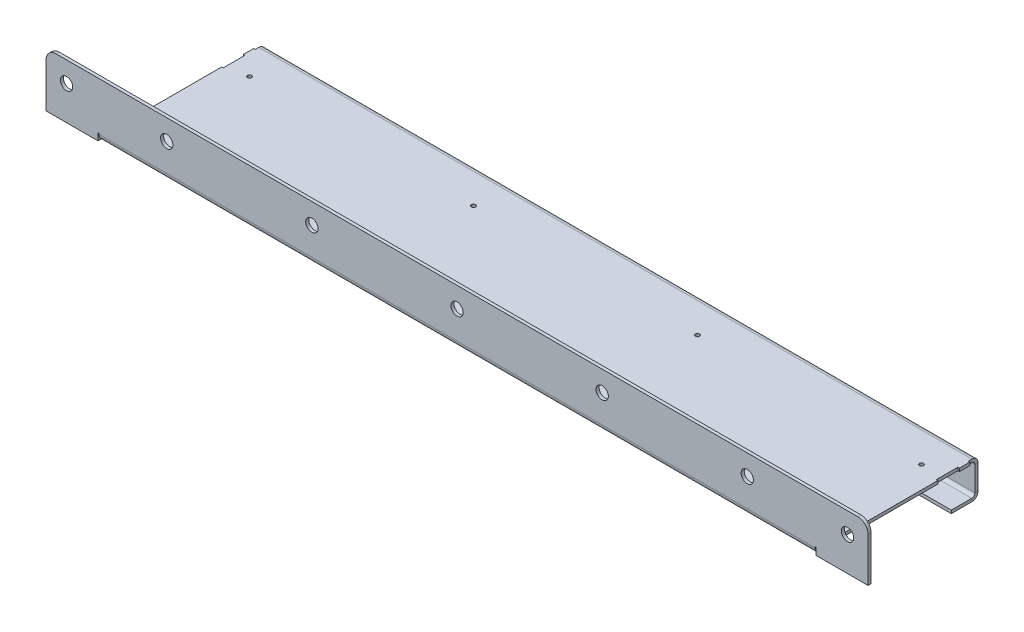
SolidWorks part; units mm, degrees
note: The reader was unsure of these and kept them because the rebuilt part matched: thickness of "Base-Flange1", "Edge-Flange1", "Edge-Flange2", "Edge-Flange3", "Sheet-Metal5", "Sheet-Metal6", "Sheet-Metal7", "Sheet-Metal8", "Sheet-Metal11", "Sheet-Metal12", "Sheet-Metal13", "Sheet-Metal15", "Sheet-Metal16", "Sheet-Metal17", "Sheet-Metal18"; flange length of "Edge-Flange1", "Edge-Flange2", "Edge-Flange3".
material "3.0 mm SS316 2B/2B"
ref_plane "Front Plane" through (0, 0, 0) normal (0, 0, 1) x (1, 0, 0)
ref_plane "Top Plane" through (0, 0, 0) normal (0, 1, 0) x (1, 0, 0)
ref_plane "Right Plane" through (0, 0, 0) normal (1, 0, 0) x (0, 0, -1)
sketch "Sketch2" plane through (0, 0, 0) normal (0, 0, 1) x (1, 0, 0)
  line L0 (400, 26.5) -> (-400, -26.5) construction
  line L1 (400, 26.5) -> (-400, 26.5)
  line L2 (400, 26.5) -> (400, -26.5)
  line L3 (400, -26.5) -> (-400, -26.5)
  line L4 (-400, 26.5) -> (-400, -26.5)
  line L5 (-400, 26.5) -> (400, -26.5) construction
  dimension "D1" = 800
  dimension "D2" = 53
base flange "Base-Flange1" sketch "Sketch2" thickness 3 reverse thickness direction no parameters "D1"=3
edge flange "Edge-Flange1" sketch "Sketch9" flange angle 90 flange length 160 flange position material inside bend radius 3 thickness 3 relief rectangular parameters "D1"=2, "D6"=10
sketch "Sketch9" plane through (0, -26.5, -3) normal (0, 1, 0) x (1, 0, 0)
  line L0 (-348.5, 16.5) -> (-347, 16.5)
  line L1 (400, 0) -> (-400, 0) construction
  line L2 (-348.5, 0) -> (-348.5, 16.5)
  line L3 (-347, 157) -> (347, 157)
  line L4 (-400, -3) -> (400, -3) construction
  line L5 (348.5, 0) -> (-348.5, 0)
  line L6 (0, 0) -> (0, 157) construction
  line L7 (-347, 16.5) -> (-347, 37.5)
  line L8 (-347, 37.5) -> (-348.5, 37.5)
  line L9 (-348.5, 116.5) -> (-347, 116.5)
  line L10 (-347, 116.5) -> (-347, 137.5)
  line L11 (-347, 137.5) -> (-348.5, 137.5)
  line L12 (-348.5, 147.5) -> (-347, 147.5)
  line L13 (-347, 147.5) -> (-347, 157)
  line L14 (-348.5, 137.5) -> (-348.5, 147.5)
  line L15 (-348.5, 37.5) -> (-348.5, 116.5)
  line L17 (-348.5, 77) -> (348.5, 77) construction
  line L18 (348.5, 37.5) -> (348.5, 116.5)
  line L19 (348.5, 137.5) -> (348.5, 147.5)
  line L20 (347, 147.5) -> (347, 157)
  line L21 (348.5, 147.5) -> (347, 147.5)
  line L22 (347, 137.5) -> (348.5, 137.5)
  line L23 (347, 116.5) -> (347, 137.5)
  line L24 (348.5, 116.5) -> (347, 116.5)
  line L25 (347, 37.5) -> (348.5, 37.5)
  line L26 (347, 16.5) -> (347, 37.5)
  line L27 (348.5, 0) -> (348.5, 16.5)
  line L28 (348.5, 16.5) -> (347, 16.5)
  line L29 (400, -3) -> (-400, -3) construction
  dimension "D1" = 80
  dimension "D2" = 160
  dimension "D3" = 21
  dimension "D4" = 100
  dimension "D5" = 1.5
  dimension "D6" = 694
  dimension "D7" = 10
bend "EdgeBend1" bend radius 3 bend angle 90 parameters "D5"=1
edge flange "Edge-Flange2" sketch "Sketch12" flange angle 90 flange length 36 flange position material inside bend radius 3 thickness 3 relief rectangular parameters "D1"=2, "D6"=10
sketch "Sketch12" plane through (0, -26.5, -160) normal (0, 0, 1) x (-1, 0, 0)
  line L0 (-348.5, 0) -> (348.5, 0) construction
  line L1 (347, 0) -> (-347, 0) construction
  line L2 (-347, 0) -> (-347, 33)
  line L3 (-347, 33) -> (347, 33)
  line L4 (347, 0) -> (347, 33)
  line L5 (347, 0) -> (-347, 0)
  line L10 (0, -6) -> (0, 33) construction
  line L11 (348.5, -6) -> (-348.5, -6) construction
bend "EdgeBend2" bend radius 3 bend angle 90 parameters "D5"=2
edge flange "Edge-Flange3" sketch "Sketch15" flange angle 90 flange length 26 flange position material inside bend radius 3 thickness 3 relief rectangular parameters "D1"=2, "D6"=10
sketch "Sketch15" plane through (0, -59.5, -157) normal (0, 1, 0) x (-1, 0, 0)
  line L1 (347, 0) -> (-347, 0) construction
  line L2 (-347, 0) -> (-347, 23)
  line L3 (-347, 23) -> (347, 23)
  line L4 (347, 23) -> (347, 0)
  line L5 (347, 0) -> (-347, 0)
bend "EdgeBend3" bend radius 3 bend angle 90 parameters "D5"=3
fillet "Fillet1" radius 10 2 edges at (-400, 26.5, -1.5) (400, 26.5, -1.5)
sketch "Sketch19" plane through (0, 0, -160) normal (0, 0, -1) x (-1, 0, 0)
  line L0 (-347, -53.5) -> (-347, -29.5) construction
  line L1 (-286.5914, -39.5) -> (-289.7957, -33.95)
  line L2 (-289.7957, -33.95) -> (-296.2043, -33.95)
  line L3 (-296.2043, -33.95) -> (-299.4086, -39.5)
  line L4 (-299.4086, -39.5) -> (-296.2043, -45.05)
  line L5 (-296.2043, -45.05) -> (-289.7957, -45.05)
  line L6 (-289.7957, -45.05) -> (-286.5914, -39.5)
  line L7 (347, -59.5) -> (-347, -59.5) construction
  circle A0 centre (-293, -39.5) radius 5.55 construction
  dimension "D1" = 11.1
  dimension "D2" = 54
  dimension "D3" = 20
extrude "Cut-Extrude2" cut sketch "Sketch19" against normal up to surface (3 mm away) normal cut yes up to face at (0, -41.5, -157)
pattern_linear "LPattern1" count 4 spacing 195.3333 along (-1, 0, 0) of "Cut-Extrude2"
sketch "Sketch20" plane through (0, 0, -3) normal (0, 0, -1) x (-1, 0, 0)
  line L0 (0, 26.5) -> (0, -59.5) construction
  line L1 (347, -59.5) -> (-347, -59.5) construction
  line L2 (-390, 26.5) -> (390, 26.5) construction
  line L3 (-400, -26.5) -> (-400, 16.5) construction
  circle A0 centre (-380, 6.5) radius 6
  circle A1 centre (380, 6.5) radius 6
  dimension "D1" = 12
  dimension "D2" = 20
  dimension "D3" = 20
extrude "Cut-Extrude3" cut sketch "Sketch20" against normal up to surface (3 mm away) normal cut yes up to face at (0, -9.6613, 0)
sketch "Sketch21" plane through (0, 0, -3) normal (0, 0, -1) x (-1, 0, 0)
  circle A0 centre (-282.5, 6.5) radius 6
  circle A1 centre (-380, 6.5) radius 6 construction
  dimension "D1" = 97.5
extrude "Cut-Extrude4" cut sketch "Sketch21" against normal up to surface (3 mm away) contours A0 normal cut yes up to face at (-386, 6.5, 0)
pattern_linear "LPattern2" count 5 spacing 141.25 along (-1, 0, 0) of "Cut-Extrude4"
sketch "Sketch22" plane through (0, -23.5, 0) normal (0, 1, 0) x (1, 0, 0)
  line L0 (390, 0) -> (-390, 0) construction
  line L1 (-347, 160) -> (347, 160) construction
  line L2 (-327, 16) -> (-327, 125) construction
  line L3 (-347, 40.5) -> (-347, 19.5) construction
  circle A0 centre (-327, 16) radius 2
  circle A1 centre (-327, 39) radius 2
  circle A2 centre (-327, 125) radius 2
  dimension "D1" = 35
  dimension "D4" = 4
  dimension "D2" = 86
  dimension "D3" = 16
  dimension "D5" = 20
extrude "Cut-Extrude5" cut sketch "Sketch22" against normal up to surface (3 mm away) normal cut yes up to face at (0, -26.5, -91.75)
pattern_linear "LPattern3" count 4 spacing 218 along (1, 0, 0) of "Cut-Extrude5"
sketch "Bend-Lines1" [suppressed] plane through (0, 0, 0) normal (0, 1, 0) x (1, 0, 0)
sketch "Bounding-Box1" [suppressed] plane through (0, 0, 0) normal (0, 1, 0) x (1, 0, 0)
sheet metal parameters "Sheet-Metal5" thickness 3 parameters "D1"=3, "D7"=5
flat pattern "Flat-Pattern5" [suppressed]
sketch "Bend-Lines2" plane through (0, 0, 0) normal (0, 1, 0) x (1, 0, 0)
sketch3d "Bounding-Box2" [suppressed]
  line L0 (-417.5, -26.5, 0) -> (417.5, -26.5, 0) construction
  line L1 (-417.5, 26.5, 0) -> (417.5, 26.5, 0) construction
  line L2 (-417.5, -26.5, 0) -> (-417.5, 26.5, 0) construction
  line L3 (417.5, -26.5, 0) -> (417.5, 26.5, 0) construction
sheet metal parameters "Sheet-Metal6" thickness 3 parameters "D1"=3, "D7"=5
flat pattern "Flat-Pattern5"
sketch "Bend-Lines2" plane through (0, 0, 0) normal (0, 0, 1) x (1, 0, 0)
  line L0 (-365.5, -23.5) -> (365.5, -23.5) construction
  line L1 (-365.5, -23.5) -> (365.5, -23.5) construction
sketch3d "Bounding-Box2" [suppressed]
  line L0 (-417.5, -180.5, 0) -> (417.5, -180.5, 0) construction
  line L1 (-417.5, 26.5, 0) -> (417.5, 26.5, 0) construction
  line L2 (-417.5, -180.5, 0) -> (-417.5, 26.5, 0) construction
  line L3 (417.5, -180.5, 0) -> (417.5, 26.5, 0) construction
bend of the flat pattern "Flatten-<EdgeBend1>1"
sheet metal parameters "Sheet-Metal7" thickness 3 parameters "D1"=3, "D7"=5
flat pattern "Flat-Pattern5"
sketch "Bend-Lines2" plane through (0, 0, 0) normal (0, 0, 1) x (1, 0, 0)
  line L0 (-450, -179.1991) -> (450, -179.1991) construction
  line L1 (-451, -23) -> (451, -23) construction
  line L2 (-450, -179.1991) -> (450, -179.1991) construction
  line L3 (-451, -23) -> (451, -23) construction
sketch3d "Bounding-Box2" [suppressed]
  line L0 (-500, -213.3982, 0) -> (500, -213.3982, 0) construction
  line L1 (-500, 25, 0) -> (500, 25, 0) construction
  line L2 (-500, -213.3982, 0) -> (-500, 25, 0) construction
  line L3 (500, -213.3982, 0) -> (500, 25, 0) construction
bend of the flat pattern "Flatten-<EdgeBend1>1"
bend of the flat pattern "Flatten-<EdgeBend2>1"
sheet metal parameters "Sheet-Metal8" thickness 3 parameters "D1"=3, "D7"=5
flat pattern "Flat-Pattern5"
sketch "Bend-Lines2" plane through (0, 0, 0) normal (0, 0, 1) x (1, 0, 0)
  line L0 (-450, -211.3982) -> (450, -211.3982) construction
  line L1 (-450, -179.1991) -> (450, -179.1991) construction
  line L2 (-451, -23) -> (451, -23) construction
  line L3 (-450, -211.3982) -> (450, -211.3982) construction
  line L4 (-450, -179.1991) -> (450, -179.1991) construction
  line L5 (-451, -23) -> (451, -23) construction
sketch3d "Bounding-Box2" [suppressed]
  line L0 (-500, -235.3982, 0) -> (500, -235.3982, 0) construction
  line L1 (-500, 25, 0) -> (500, 25, 0) construction
  line L2 (-500, -235.3982, 0) -> (-500, 25, 0) construction
  line L3 (500, -235.3982, 0) -> (500, 25, 0) construction
bend of the flat pattern "Flatten-<EdgeBend1>1"
bend of the flat pattern "Flatten-<EdgeBend2>1"
bend of the flat pattern "Flatten-<EdgeBend3>1"
sheet metal parameters "Sheet-Metal11" thickness 3 parameters "D1"=3, "D7"=5
flat pattern "Flat-Pattern5"
sketch "Bend-Lines2" plane through (0, 0, 0) normal (0, 0, 1) x (1, 0, 0)
  line L0 (-450, -211.3982) -> (450, -211.3982) construction
  line L1 (-450, -179.1991) -> (450, -179.1991) construction
  line L2 (-451, -23) -> (451, -23) construction
  line L3 (-450, -211.3982) -> (450, -211.3982) construction
  line L4 (-450, -179.1991) -> (450, -179.1991) construction
  line L5 (-451, -23) -> (451, -23) construction
sketch3d "Bounding-Box2" [suppressed]
  line L0 (-500, -235.3982, 0) -> (500, -235.3982, 0) construction
  line L1 (-500, 25, 0) -> (500, 25, 0) construction
  line L2 (-500, -235.3982, 0) -> (-500, 25, 0) construction
  line L3 (500, -235.3982, 0) -> (500, 25, 0) construction
bend of the flat pattern "Flatten-<EdgeBend1>1"
bend of the flat pattern "Flatten-<EdgeBend2>1"
bend of the flat pattern "Flatten-<EdgeBend3>1"
sheet metal parameters "Sheet-Metal12" thickness 3 parameters "D1"=3, "D7"=5
flat pattern "Flat-Pattern5"
sketch "Bend-Lines2" plane through (0, 0, 0) normal (0, 0, 1) x (1, 0, 0)
  line L0 (-450, -211.3982) -> (450, -211.3982) construction
  line L1 (-450, -179.1991) -> (450, -179.1991) construction
  line L2 (-451, -23) -> (451, -23) construction
  line L3 (-450, -211.3982) -> (450, -211.3982) construction
  line L4 (-450, -179.1991) -> (450, -179.1991) construction
  line L5 (-451, -23) -> (451, -23) construction
sketch3d "Bounding-Box2" [suppressed]
  line L0 (-500, -235.3982, 0) -> (500, -235.3982, 0) construction
  line L1 (-500, 25, 0) -> (500, 25, 0) construction
  line L2 (-500, -235.3982, 0) -> (-500, 25, 0) construction
  line L3 (500, -235.3982, 0) -> (500, 25, 0) construction
bend of the flat pattern "Flatten-<EdgeBend1>1"
bend of the flat pattern "Flatten-<EdgeBend2>1"
bend of the flat pattern "Flatten-<EdgeBend3>1"
sheet metal parameters "Sheet-Metal13" thickness 3 parameters "D1"=3, "D7"=5
flat pattern "Flat-Pattern5"
sketch "Bend-Lines2" plane through (0, 0, 0) normal (0, 0, 1) x (1, 0, 0)
  line L0 (-450, -211.3982) -> (450, -211.3982) construction
  line L1 (-450, -179.1991) -> (450, -179.1991) construction
  line L2 (-451, -23) -> (451, -23) construction
  line L3 (-450, -211.3982) -> (450, -211.3982) construction
  line L4 (-450, -179.1991) -> (450, -179.1991) construction
  line L5 (-451, -23) -> (451, -23) construction
sketch3d "Bounding-Box2" [suppressed]
  line L0 (-500, -235.3982, 0) -> (500, -235.3982, 0) construction
  line L1 (-500, 25, 0) -> (500, 25, 0) construction
  line L2 (-500, -235.3982, 0) -> (-500, 25, 0) construction
  line L3 (500, -235.3982, 0) -> (500, 25, 0) construction
bend of the flat pattern "Flatten-<EdgeBend1>1"
bend of the flat pattern "Flatten-<EdgeBend2>1"
bend of the flat pattern "Flatten-<EdgeBend3>1"
sheet metal parameters "Sheet-Metal15" thickness 3 parameters "D1"=3, "D7"=5
flat pattern "Flat-Pattern5"
sketch "Bend-Lines2" plane through (0, 0, 0) normal (0, 0, 1) x (1, 0, 0)
  line L0 (-450, -211.3982) -> (450, -211.3982) construction
  line L1 (-450, -179.1991) -> (450, -179.1991) construction
  line L2 (-451, -23) -> (451, -23) construction
  line L3 (-450, -211.3982) -> (450, -211.3982) construction
  line L4 (-450, -179.1991) -> (450, -179.1991) construction
  line L5 (-451, -23) -> (451, -23) construction
sketch3d "Bounding-Box2" [suppressed]
  line L0 (-500, -235.3982, 0) -> (500, -235.3982, 0) construction
  line L1 (-500, 25, 0) -> (500, 25, 0) construction
  line L2 (-500, -235.3982, 0) -> (-500, 25, 0) construction
  line L3 (500, -235.3982, 0) -> (500, 25, 0) construction
bend of the flat pattern "Flatten-<EdgeBend1>1"
bend of the flat pattern "Flatten-<EdgeBend2>1"
bend of the flat pattern "Flatten-<EdgeBend3>1"
sheet metal parameters "Sheet-Metal16" thickness 3 parameters "D1"=3, "D7"=5
flat pattern "Flat-Pattern5" [suppressed]
sketch "Bend-Lines2" plane through (0, 0, 0) normal (0, 0, 1) x (1, 0, 0)
  line L0 (-375, -211.0114) -> (375, -211.0114) construction
  line L1 (-375, -179) -> (375, -179) construction
  line L2 (-376, -23) -> (376, -23) construction
  line L3 (-375, -211.0114) -> (375, -211.0114) construction
  line L4 (-375, -179) -> (375, -179) construction
  line L5 (-376, -23) -> (376, -23) construction
sketch3d "Bounding-Box2" [suppressed]
  line L0 (-425, -235.0114, 0) -> (425, -235.0114, 0) construction
  line L1 (-425, 25, 0) -> (425, 25, 0) construction
  line L2 (-425, -235.0114, 0) -> (-425, 25, 0) construction
  line L3 (425, -235.0114, 0) -> (425, 25, 0) construction
bend of the flat pattern "Flatten-<EdgeBend1>1"
bend of the flat pattern "Flatten-<EdgeBend2>1"
bend of the flat pattern "Flatten-<EdgeBend3>1"
sketch "Sketch16-1" plane through (0, -21, -2) normal (0, 0, -1) x (1, 0, 0)
  line L0 (376, 80) -> (-376, 80) construction
  line L3 (376, 19.5) -> (376, 40.5)
  line L4 (376, 19.5) -> (375, 19.5)
  line L5 (375, 19.5) -> (375, 40.5)
  line L6 (375, 40.5) -> (376, 40.5)
  line L7 (376, 30) -> (-376, 30) construction
  line L8 (376, 130) -> (-376, 130) construction
  line L9 (375, 119.5) -> (376, 119.5)
  line L10 (375, 140.5) -> (375, 119.5)
  line L11 (376, 140.5) -> (375, 140.5)
  line L12 (376, 140.5) -> (376, 119.5)
  line L13 (415, -46) -> (-415, -46)
  line L14 (0, 0) -> (0, 160) construction
  line L17 (-376, 140.5) -> (-376, 119.5)
  line L18 (-376, 140.5) -> (-375, 140.5)
  line L19 (-375, 140.5) -> (-375, 119.5)
  line L20 (-375, 119.5) -> (-376, 119.5)
  line L21 (-375, 40.5) -> (-376, 40.5)
  line L22 (-375, 19.5) -> (-375, 40.5)
  line L23 (-376, 19.5) -> (-375, 19.5)
  line L24 (-376, 19.5) -> (-376, 40.5)
  line L27 (376, 154.6) -> (375, 154.6)
  line L28 (376, 154.6) -> (376, 150.5)
  line L29 (376, 150.5) -> (375, 150.5)
  line L30 (375, 154.6) -> (375, 150.5)
  line L31 (-376, 154.6) -> (-375, 154.6)
  line L32 (-376, 154.6) -> (-376, 150.5)
  line L34 (-376, 150.5) -> (-375, 150.5)
  line L35 (-375, 154.6) -> (-375, 150.5)
  dimension "D1" = 21
  dimension "D2" = 50
  dimension "D3" = 1
  dimension "D4" = 126
  dimension "D5" = 10
sheet metal parameters "Sheet-Metal17" thickness 3 parameters "D1"=3, "D7"=5
flat pattern "Flat-Pattern5"
sketch "Bend-Lines2" plane through (0, 0, 0) normal (0, 0, 1) x (1, 0, 0)
  line L0 (-375, -211.0114) -> (375, -211.0114) construction
  line L1 (-375, -179) -> (375, -179) construction
  line L2 (-376, -23) -> (376, -23) construction
  line L3 (-375, -211.0114) -> (375, -211.0114) construction
  line L4 (-375, -179) -> (375, -179) construction
  line L5 (-376, -23) -> (376, -23) construction
sketch3d "Bounding-Box2" [suppressed]
  line L0 (-425, -235.0114, 0) -> (425, -235.0114, 0) construction
  line L1 (-425, 25, 0) -> (425, 25, 0) construction
  line L2 (-425, -235.0114, 0) -> (-425, 25, 0) construction
  line L3 (425, -235.0114, 0) -> (425, 25, 0) construction
bend of the flat pattern "Flatten-<EdgeBend1>1"
bend of the flat pattern "Flatten-<EdgeBend2>1"
bend of the flat pattern "Flatten-<EdgeBend3>1"
sheet metal parameters "Sheet-Metal18" thickness 3 parameters "D1"=3, "D7"=5
flat pattern "Flat-Pattern5"
sketch "Bend-Lines2" plane through (0, 0, 0) normal (0, 0, 1) x (1, 0, 0)
  line L0 (-347, -207.5) -> (347, -207.5) construction
  line L1 (-347, -177.5) -> (347, -177.5) construction
  line L2 (-348.5, -23.5) -> (348.5, -23.5) construction
  line L3 (-347, -207.5) -> (347, -207.5) construction
  line L4 (-347, -177.5) -> (347, -177.5) construction
  line L5 (-348.5, -23.5) -> (348.5, -23.5) construction
sketch3d "Bounding-Box2" [suppressed]
  line L0 (-400, -230.5, 0) -> (400, -230.5, 0) construction
  line L1 (-400, 26.5, 0) -> (400, 26.5, 0) construction
  line L2 (-400, -230.5, 0) -> (-400, 26.5, 0) construction
  line L3 (400, -230.5, 0) -> (400, 26.5, 0) construction
bend of the flat pattern "Flatten-<EdgeBend1>1"
bend of the flat pattern "Flatten-<EdgeBend2>1"
bend of the flat pattern "Flatten-<EdgeBend3>1"
